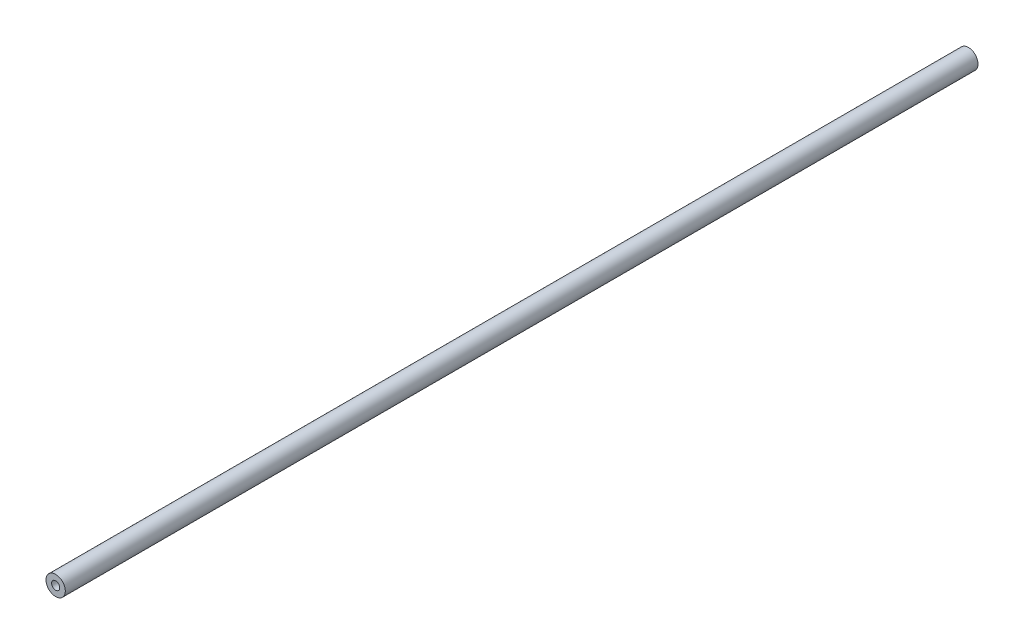
SolidWorks part; units mm, degrees
ref_plane "Front Plane" through (0, 0, 0) normal (0, 0, 1) x (1, 0, 0)
ref_plane "Top Plane" through (0, 0, 0) normal (0, 1, 0) x (1, 0, 0)
ref_plane "Right Plane" through (0, 0, 0) normal (1, 0, 0) x (0, 0, -1)
sketch "Sketch1" plane through (0, 0, 0) normal (0, 0, 1) x (1, 0, 0)
  circle A1 centre (0, 0) radius 4.7625
  dimension "D2" = 9.525
extrude "Boss-Extrude1" add sketch "Sketch1" along normal blind 450.85 contours A1 region at (0, 0, 0)
hole_wizard "#10-32 Tapped Hole1" positions "3DSketch1" profile "Sketch2" tap size "#10-32" standard "ANSI Inch"
sketch3d "3DSketch1"
  line L0 (0, 0, 450.85) -> (0, 0, 0) construction
  circle A3 centre (0, 0, 0) radius 4.7625 construction
  point P0 (0, 0, 450.85)
  point P7 (0, 0, 0)
  point P10 (0, 0, 0)
  point P12 (0, 0, 0)
  point P14 (0, 0, 0)
  point P35 (0, 0, 4.7625)
sketch "Sketch2" plane through (0, 0, 450.85) normal (1, 0, 0) x (0, -1, 0)
  line L0 (0, 0) -> (0, 16.2908)
  line L1 (0, 16.2908) -> (2.0193, 15.0774)
  line L2 (2.0193, 15.0774) -> (2.0193, 0)
  line L5 (2.0193, 0) -> (0, 0)
  line L10 (0, 16.2908) -> (-2.0193, 15.0774) construction
  line L11 (0, -6.35) -> (0, 107.95) construction
  dimension "Tap Drill Dia." = 4.0386
  dimension "Tap Drill Depth" = 15.0774
  dimension "Drill Angle" = 118
cosmetic thread "Hole Thread4" parameters "D1"=12.7, "D2"=4.826
cosmetic thread "Hole Thread5" parameters "D1"=12.7, "D2"=4.826
